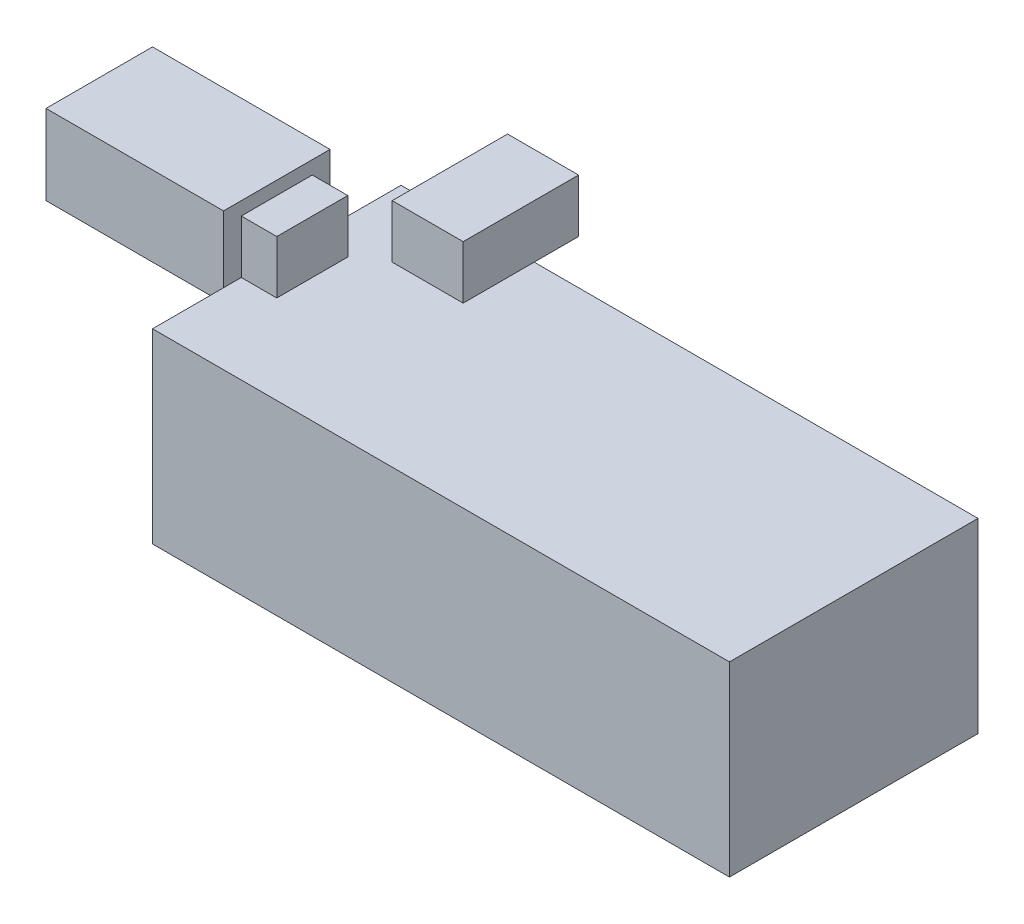
SolidWorks part; units mm, degrees
ref_plane "Front Plane" through (0, 0, 0) normal (0, 0, 1) x (1, 0, 0)
ref_plane "Top Plane" through (0, 0, 0) normal (0, 1, 0) x (1, 0, 0)
ref_plane "Right Plane" through (0, 0, 0) normal (1, 0, 0) x (0, 0, -1)
sketch "Sketch1" plane through (0, 0, 0) normal (0, 1, 0) x (1, 0, 0)
  line L1 (32.5, -14) -> (-32.5, -14)
  line L2 (32.5, -14) -> (32.5, 14)
  line L3 (32.5, 14) -> (-32.5, 14)
  line L4 (-32.5, -14) -> (-32.5, 14)
  line L5 (32.5, -14) -> (-32.5, 14) construction
  line L6 (32.5, 14) -> (-32.5, -14) construction
  point P0 (0, 0)
  dimension "D1" = 65
  dimension "D2" = 28
extrude "Boss-Extrude1" add sketch "Sketch1" against normal blind 21
sketch "Sketch3" plane through (0, 0, 0) normal (0, 1, 0) x (1, 0, 0)
  line L0 (-32.5, 14) -> (-32.5, -14) construction
  line L1 (-32.5, -4) -> (-28.5, -4)
  line L2 (-32.5, -4) -> (-32.5, 4)
  line L3 (-32.5, 4) -> (-28.5, 4)
  line L4 (-28.5, -4) -> (-28.5, 4)
  line L5 (32.5, 14) -> (-32.5, 14) construction
  line L6 (-25.5, 14) -> (-17.5, 14)
  line L7 (-25.5, 14) -> (-25.5, 6)
  line L8 (-25.5, 6) -> (-17.5, 6)
  line L9 (-17.5, 14) -> (-17.5, 6)
  dimension "D1" = 4
  dimension "D2" = 18
  dimension "D3" = 10
  dimension "D4" = 8
  dimension "D5" = 8
  dimension "D6" = 15
extrude "Boss-Extrude2" add sketch "Sketch3" along normal blind 6 contours L4 L3 L2 L1
extrude "Boss-Extrude3" add sketch "Sketch3<3>" along normal blind 6 contours L9 L8 L7 L6
sketch "Sketch3<3>" plane through (0, 0, 0) normal (0, 1, 0) x (1, 0, 0) same geometry as "Sketch3"
sketch "Sketch4" plane through (-32.5, 0, 0) normal (-1, 0, 0) x (0, 0, 1)
  line L0 (4, 6) -> (4, 0) construction
  line L1 (4, 6) -> (-4, 6) construction
  line L2 (4, 6) -> (4, 0)
  line L3 (4, 6) -> (-4, 6)
  line L4 (-4, 3) -> (4, 3)
  line L5 (-6, -1.5) -> (6, -1.5)
  line L6 (-6, -1.5) -> (-6, 7.5)
  line L7 (-6, 7.5) -> (6, 7.5)
  line L8 (6, -1.5) -> (6, 7.5)
  line L9 (-6, -1.5) -> (6, 7.5) construction
  line L10 (-6, 7.5) -> (6, -1.5) construction
  line L11 (-4, 6) -> (-4, 0) construction
  point P2 (0, 3)
  point P13 (0, 3)
  line M5 (-4, 0) -> (-14, 0)
  line M9 (14, 0) -> (4, 0)
  line M10 (4, 0) -> (4, 6)
  line M11 (4, 6) -> (-4, 6)
  line M12 (-4, 6) -> (-4, 0)
  dimension "D1" = 12
  dimension "D2" = 9
extrude "Boss-Extrude4" add sketch "Sketch4" along normal blind 20 contours L8 L7 L6 L2 M9 M5 M12 M11 M10 | L4 L2 M12 M11 | L5 L8 L4 L6 M9 M10 M12 M5 region at (-32.5, 6.1415, 0) region at (-32.5, 4.5, 0) region at (-32.5, 0.5357, 0)
sketch "Sketch5" plane through (0, 0, -14) normal (0, 0, -1) x (-1, 0, 0)
  line L1 (17.5, 6) -> (25.5, 6)
  line L2 (17.5, 6) -> (17.5, 0)
  line L3 (17.5, 0) -> (25.5, 0)
  line L4 (25.5, 6) -> (25.5, 0)
extrude "Boss-Extrude5" add sketch "Sketch5" along normal blind 5
